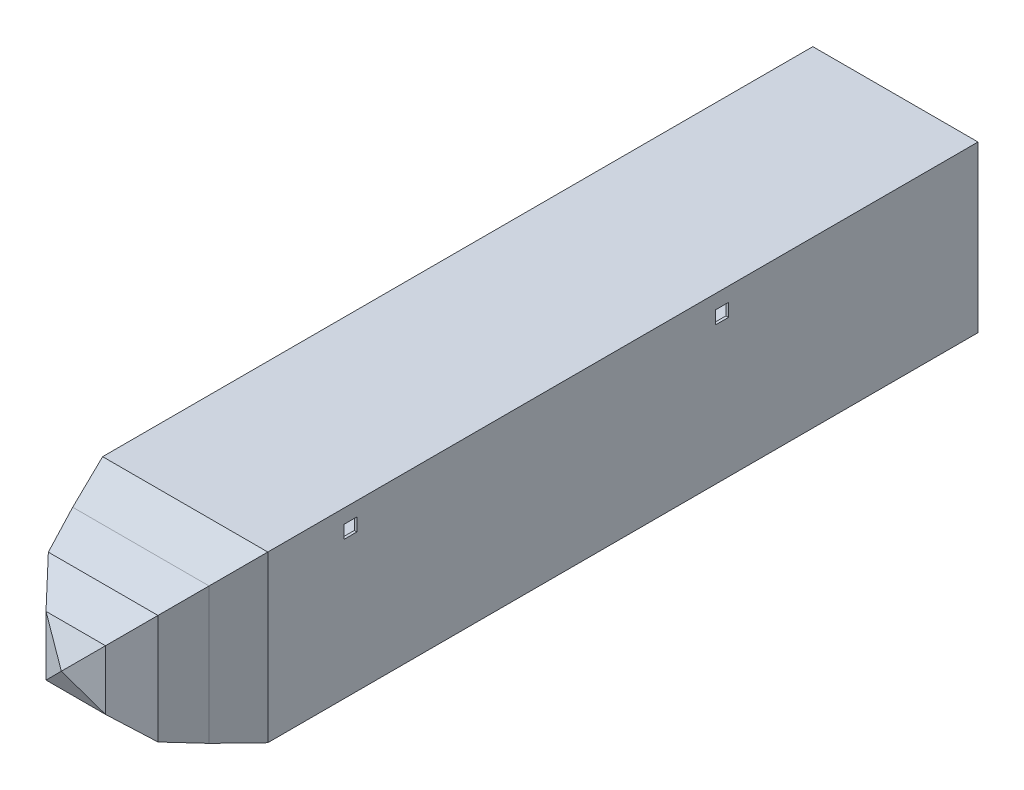
SolidWorks part; units mm, degrees
ref_plane "Front Plane" through (0, 0, 0) normal (0, 0, 1) x (1, 0, 0)
ref_plane "Top Plane" through (0, 0, 0) normal (0, 1, 0) x (1, 0, 0)
ref_plane "Right Plane" through (0, 0, 0) normal (1, 0, 0) x (0, 0, -1)
sketch "Sketch1" plane through (0, 0, 0) normal (0, 0, 1) x (1, 0, 0)
  line L1 (-50.8, -50.8) -> (50.8, -50.8)
  line L2 (-50.8, -50.8) -> (-50.8, 50.8)
  line L3 (-50.8, 50.8) -> (50.8, 50.8)
  line L4 (50.8, -50.8) -> (50.8, 50.8)
  line L5 (-50.8, -50.8) -> (50.8, 50.8) construction
  line L6 (-50.8, 50.8) -> (50.8, -50.8) construction
  point P0 (0, 0)
  dimension "D1" = 101.6
  dimension "D2" = 101.6
extrude "Boss-Extrude1" add sketch "Sketch1" along normal blind 436.88 contours L2 L1 L4 L3
ref_plane "Plane1" through (0, 0, 464.1566) normal (0, 0, 1) x (1, 0, 0)
sketch "Sketch3" plane through (0, 0, 464.1566) normal (0, 0, 1) x (1, 0, 0)
  line L1 (-41.9373, -41.9373) -> (41.9373, -41.9373)
  line L2 (-41.9373, -41.9373) -> (-41.9373, 41.9373)
  line L3 (-41.9373, 41.9373) -> (41.9373, 41.9373)
  line L4 (41.9373, -41.9373) -> (41.9373, 41.9373)
  line L5 (-41.9373, -41.9373) -> (41.9373, 41.9373) construction
  line L6 (-41.9373, 41.9373) -> (41.9373, -41.9373) construction
  point P0 (0, 0)
  dimension "D1" = 83.8746
  dimension "D2" = 83.8746
sketch "Sketch5" plane through (0, 0, 436.88) normal (0, 0, 1) x (1, 0, 0)
  line L0 (50.8, -50.8) -> (50.8, 50.8) construction
  line L1 (-50.8, 50.8) -> (50.8, 50.8) construction
  line L2 (-50.8, -50.8) -> (-50.8, 50.8) construction
  line L3 (-50.8, -50.8) -> (50.8, -50.8) construction
  line L4 (50.8, -50.8) -> (50.8, 50.8)
  line L5 (-50.8, 50.8) -> (50.8, 50.8)
  line L6 (-50.8, -50.8) -> (-50.8, 50.8)
  line L7 (-50.8, -50.8) -> (50.8, -50.8)
  dimension "D1" = 101.6
  dimension "D2" = 101.6
loft "Loft2" add profiles "Sketch5", "Sketch3" connector at (-50.8, 50.8, 436.88) connector at (-41.9373, 41.9373, 464.1566)
ref_plane "Plane2" through (0, 0, 487.3594) normal (0, 0, 1) x (1, 0, 0)
sketch "Sketch6" plane through (0, 0, 487.3594) normal (0, 0, 1) x (1, 0, 0)
  line L1 (-33.716, -33.716) -> (33.716, -33.716)
  line L2 (-33.716, -33.716) -> (-33.716, 33.716)
  line L3 (-33.716, 33.716) -> (33.716, 33.716)
  line L4 (33.716, -33.716) -> (33.716, 33.716)
  line L5 (-33.716, -33.716) -> (33.716, 33.716) construction
  line L6 (-33.716, 33.716) -> (33.716, -33.716) construction
  point P0 (0, 0)
loft "Loft3" add profiles "Sketch3<6>", "Sketch6" connector at (-41.9373, 41.9373, 464.1566) connector at (-33.716, 33.716, 487.3594)
sketch "Sketch3<6>" plane through (0, 0, 464.1566) normal (0, 0, 1) x (1, 0, 0) same geometry as "Sketch3"
ref_plane "Plane3" through (0, 0, 504.2173) normal (0, 0, 1) x (1, 0, 0)
sketch "Sketch7" plane through (0, 0, 504.2173) normal (0, 0, 1) x (1, 0, 0)
  line L5 (-41.9373, -41.9373) -> (41.9373, 41.9373) construction
  line L6 (-18.3041, -18.3041) -> (18.3041, -18.3041)
  line L8 (-18.3041, -18.3041) -> (-18.3041, 18.3041)
  line L9 (-18.3041, 18.3041) -> (18.3041, 18.3041)
  line L10 (18.3041, -18.3041) -> (18.3041, 18.3041)
  line L11 (-18.3041, -18.3041) -> (18.3041, 18.3041) construction
  line L12 (-18.3041, 18.3041) -> (18.3041, -18.3041) construction
  point P1 (0, 0)
loft "Loft4" add profiles "Sketch6<4>", "Sketch7" connector at (33.716, 33.716, 487.3594) connector at (18.3041, 18.3041, 504.2173)
sketch "Sketch6<4>" plane through (0, 0, 487.3594) normal (0, 0, 1) x (1, 0, 0) same geometry as "Sketch6"
sketch3d "3DSketch1" plane through (0, 0, 0) normal (0, 0, 1) x (1, 0, 0)
  dimension "D1" = 8.8627
sketch "Sketch8" plane through (0, 0, 513.08) normal (0, 0, 1) x (1, 0, 0)
  point P0 (0, 0)
loft "Loft5" add profiles "Sketch8", "Sketch7<5>"
sketch "Sketch7<5>" plane through (0, 0, 504.2173) normal (0, 0, 1) x (1, 0, 0) same geometry as "Sketch7"
shell "Shell1" thickness 1.5875 removed face at (0, 0, 0)
sketch "Sketch9" plane through (50.8, 0, 0) normal (1, 0, 0) x (0, 0, -1)
  line L0 (-436.88, 50.8) -> (-436.88, 38.1)
  line L1 (-436.88, -50.8) -> (-436.88, 50.8) construction
  line L2 (-436.88, 38.1) -> (-386.08, 38.1)
  line L3 (-386.08, 38.1) -> (-157.48, 38.1)
  line L5 (-390.0805, 34.0995) -> (-382.0795, 34.0995)
  line L6 (-390.0805, 34.0995) -> (-390.0805, 42.1005)
  line L7 (-390.0805, 42.1005) -> (-382.0795, 42.1005)
  line L8 (-382.0795, 34.0995) -> (-382.0795, 42.1005)
  line L9 (-390.0805, 34.0995) -> (-382.0795, 42.1005) construction
  line L10 (-390.0805, 42.1005) -> (-382.0795, 34.0995) construction
  line L11 (-161.4805, 34.0995) -> (-153.4795, 34.0995)
  line L12 (-161.4805, 34.0995) -> (-161.4805, 42.1005)
  line L13 (-161.4805, 42.1005) -> (-153.4795, 42.1005)
  line L14 (-153.4795, 34.0995) -> (-153.4795, 42.1005)
  line L15 (-161.4805, 34.0995) -> (-153.4795, 42.1005) construction
  line L16 (-161.4805, 42.1005) -> (-153.4795, 34.0995) construction
  dimension "D4" = 8.001
  dimension "D5" = 8.001
  dimension "D1" = 12.7
  dimension "D2" = 50.8
  dimension "D3" = 228.6
  dimension "D6" = 8.001
  dimension "D7" = 8.001
extrude "Cut-Extrude1" cut sketch "Sketch9" against normal through all contours L5 L8 L3 L2 L6 | L3 L8 L7 L6 L2 | L11 L14 L13 L12 region at (50.8, 40.1002, 386.08) region at (50.8, 36.0997, 386.08) region at (50.8, 40.1002, 161.3673)
equation "\"Fuse_Diam\"= 4"
equation "\"D2@Sketch1\"=\"Fuse_Diam\""
equation "\"D1@Sketch1\"=\"Fuse_Diam\""
equation "\"Magic Line\"= 3 / ( cos ( 18 ) + cos ( 2 * 18 ) + cos ( 3 * 18 ) + cos ( 4 * 18 ) )"
equation "\"Second Stage Cone\"= 3.30215"
equation "\"D1@Sketch3\"=\"Second Stage Cone\""
equation "\"D2@Sketch3\"=\"Second Stage Cone\""
